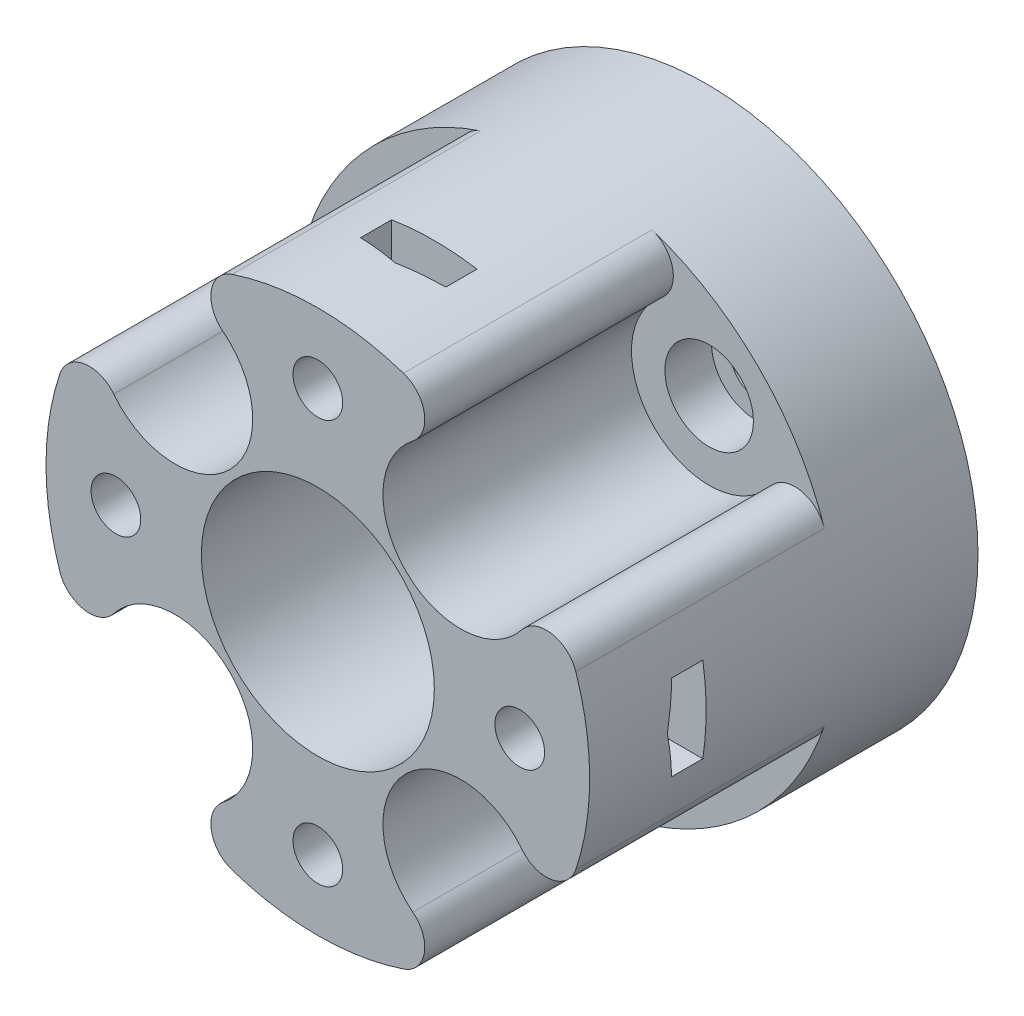
SolidWorks part; units mm, degrees
ref_plane "Front Plane" through (0, 0, 0) normal (1, 0, 0) x (0, 1, 0)
ref_plane "Top Plane" through (0, 0, 0) normal (0, 0, 1) x (0, 1, 0)
ref_plane "Right Plane" through (0, 0, 0) normal (0, 1, 0) x (-1, 0, 0)
sketch "Sketch1" plane through (0, 0, 0) normal (0, 0, 1) x (0, 1, 0)
  line L0 (0, 0) -> (9.1924, 9.1924) construction
  circle A0 centre (0, 0) radius 17.5
  circle A1 centre (0, 0) radius 13 construction
  circle A2 centre (9.1924, 9.1924) radius 1.6
  circle A3 centre (9.1924, 9.1924) radius 2.85
  circle A4 centre (9.1924, -9.1924) radius 2.85
  circle A5 centre (9.1924, -9.1924) radius 1.6
  circle A6 centre (-9.1924, -9.1924) radius 2.85
  circle A7 centre (-9.1924, -9.1924) radius 1.6
  circle A8 centre (-9.1924, 9.1924) radius 2.85
  circle A9 centre (-9.1924, 9.1924) radius 1.6
  point P19 (0, 0)
  dimension "D1" = 35
  dimension "D2" = 26
  dimension "D3" = 3.2
  dimension "D4" = 5.7
  dimension "D5" = 4
extrude "Boss-Extrude1" add sketch "Sketch1" along normal blind 25 contours A0 A8 A6 A4 A3 region at (0, 0, 0)
extrude "Boss-Extrude2" add sketch "Sketch1<3>" along normal blind 6 contours A6 A7 | A8 A9 | A4 A5 | A3 A2 region at (-9.1924, 6.423, 0) region at (9.1924, 6.423, 0) region at (9.1924, -11.9618, 0) region at (-9.1924, -11.9618, 0)
sketch "Sketch1<3>" plane through (0, 0, 0) normal (0, 0, 1) x (0, 1, 0) same geometry as "Sketch1"
sketch "Sketch2" plane through (0, 0, 25) normal (0, 0, 1) x (1, 0, 0)
  circle A0 centre (-9.1924, 9.1924) radius 5
  circle A1 centre (9.1924, 9.1924) radius 5
  circle A2 centre (9.1924, -9.1924) radius 5
  circle A3 centre (-9.1924, -9.1924) radius 5
  dimension "D1" = 10
  dimension "D2" = 2
  dimension "D3" = 2
extrude "Cut-Extrude1" cut sketch "Sketch2" against normal offset from surface (16 mm away) 9 up to face at (17.5, 0, 0)
fillet "Fillet1" radius 2 8 edges at (14.0286, 10.4618, 17) (-14.0286, 10.4618, 17) (-10.4618, 14.0286, 17) (10.4618, 14.0286, 17) (14.0286, -10.4618, 17) (10.4618, -14.0286, 17) (-10.4618, -14.0286, 17) (-14.0286, -10.4618, 17)
sketch "Sketch3" plane through (0, 0, 25) normal (0, 0, 1) x (1, 0, 0)
  line L0 (-2.75, 15.75) -> (-2.75, 17.2826)
  line L2 (-2.75, 15.75) -> (-2.75, 10.25)
  line L3 (-2.75, 10.25) -> (2.75, 10.25)
  line L4 (2.75, 15.75) -> (2.75, 10.25)
  line L5 (-2.75, 15.75) -> (2.75, 10.25) construction
  line L6 (-2.75, 10.25) -> (2.75, 15.75) construction
  line L7 (2.75, 15.75) -> (2.75, 17.2826)
  line L8 (15.75, -2.75) -> (10.25, -2.75)
  line L9 (10.25, 2.75) -> (10.25, -2.75)
  line L10 (15.75, 2.75) -> (10.25, 2.75)
  line L11 (15.75, 2.75) -> (17.2826, 2.75)
  line L12 (15.75, -2.75) -> (17.2826, -2.75)
  line L13 (-2.75, -15.75) -> (-2.75, -10.25)
  line L14 (2.75, -10.25) -> (-2.75, -10.25)
  line L15 (2.75, -15.75) -> (2.75, -10.25)
  line L16 (2.75, -15.75) -> (2.75, -17.2826)
  line L17 (-2.75, -15.75) -> (-2.75, -17.2826)
  line L18 (-15.75, 2.75) -> (-10.25, 2.75)
  line L19 (-10.25, -2.75) -> (-10.25, 2.75)
  line L20 (-15.75, -2.75) -> (-10.25, -2.75)
  line L21 (-15.75, -2.75) -> (-17.2826, -2.75)
  line L22 (-15.75, 2.75) -> (-17.2826, 2.75)
  circle A0 centre (0, 0) radius 13 construction
  circle A2 centre (0, 13) radius 1.6
  arc A3 (5.5152, 16.6082) -> (-5.5152, 16.6082) centre (0, 0) ccw construction
  arc A4 (-2.75, 17.2826) -> (2.75, 17.2826) centre (0, 0) cw
  arc A5 (17.2826, 2.75) -> (17.2826, -2.75) centre (0, 0) cw
  circle A6 centre (13, 0) radius 1.6
  arc A7 (2.75, -17.2826) -> (-2.75, -17.2826) centre (0, 0) cw
  circle A8 centre (0, -13) radius 1.6
  arc A9 (-17.2826, -2.75) -> (-17.2826, 2.75) centre (0, 0) cw
  circle A10 centre (-13, 0) radius 1.6
  point P41 (0, 0)
  dimension "D1" = 26
  dimension "D2" = 3.2
  dimension "D3" = 5.5
  dimension "D4" = 5.5
  dimension "D5" = 4
extrude "Cut-Extrude2" cut sketch "Sketch3" against normal blind 2.5 from offset 5 offset against normal yes
extrude "Cut-Extrude3" cut sketch "Sketch3<2>" against normal blind 10 contours A10 | A2 | A6 | A8 region at (0, 13, 25) region at (13, 0, 25) region at (0, -13, 25) region at (-13, 0, 25)
sketch "Sketch3<2>" plane through (0, 0, 25) normal (0, 0, 1) x (1, 0, 0) same geometry as "Sketch3"
chamfer "Chamfer1" distance 2.75 distance2 0.5 8 edges at (-13.7663, -2.75, 20) (-2.75, 13.7663, 20) (2.75, 13.7663, 20) (13.7663, 2.75, 20) (13.7663, -2.75, 20) (2.75, -13.7663, 20) (-2.75, -13.7663, 20) (-13.7663, 2.75, 20) first distance on face at (-14.6, 0, 20) first distance on face at (-1.6, 13, 20) first distance on face at (11.4, 0, 20) first distance on face at (-1.6, -13, 20)
sketch "Sketch4" plane through (0, 0, 25) normal (0, 0, 1) x (1, 0, 0)
  circle A0 centre (0, 0) radius 7.5
  point P2 (0, 0)
  dimension "D1" = 15
extrude "Cut-Extrude4" cut sketch "Sketch4" against normal through all contours A0
